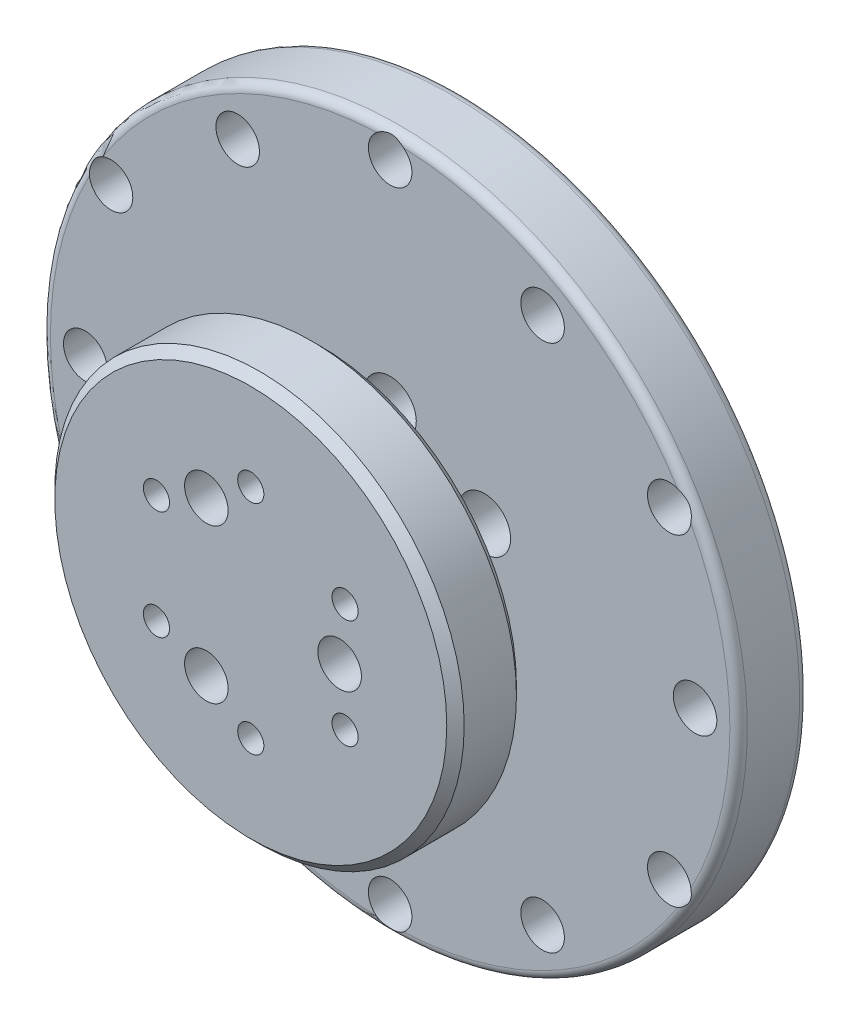
SolidWorks part; units mm, degrees
ref_plane "前视基准面" through (0, 0, 0) normal (0, 0, 1) x (1, 0, 0)
ref_plane "上视基准面" through (0, 0, 0) normal (0, 1, 0) x (1, 0, 0)
ref_plane "右视基准面" through (0, 0, 0) normal (1, 0, 0) x (0, 0, -1)
sketch "草图1" plane through (0, 0, 0) normal (0, 0, 1) x (1, 0, 0)
  circle A0 centre (0, 0) radius 23.5
extrude "凸台-拉伸3" add sketch "草图1" along normal blind 8
sketch "草图2" plane through (0, 0, 0) normal (0, 0, -1) x (-1, 0, 0)
  circle A1 centre (0, 12.5) radius 0.75
  circle A2 centre (10.8253, 6.25) radius 0.75
  circle A3 centre (10.8253, -6.25) radius 0.75
  circle A4 centre (0, -12.5) radius 0.75
  circle A5 centre (-10.8253, -6.25) radius 0.75
  circle A6 centre (-10.8253, 6.25) radius 0.75
extrude "切除-拉伸1" cut sketch "草图2" against normal blind 22
sketch "草图3" plane through (0, 0, 0) normal (0, 0, -1) x (-1, 0, 0)
  circle A0 centre (-10.8253, 6.25) radius 1.5
extrude "切除-拉伸2" cut sketch "草图3" against normal blind 22
sketch "草图4" plane through (0, 0, 0) normal (0, 0, -1) x (-1, 0, 0)
  circle A0 centre (0, 12.5) radius 1.5
extrude "切除-拉伸3" cut sketch "草图4" against normal blind 22
sketch "草图6" plane through (0, 0, 0) normal (0, 0, -1) x (-1, 0, 0)
  circle A0 centre (10.8253, 6.25) radius 1.5
extrude "切除-拉伸4" cut sketch "草图6" against normal blind 22
sketch "草图7" plane through (0, 0, 0) normal (0, 0, -1) x (-1, 0, 0)
  circle A0 centre (-10.8253, -6.25) radius 1.5
extrude "切除-拉伸5" cut sketch "草图7" against normal blind 22 contours A0
sketch "草图8" plane through (0, 0, 0) normal (0, 0, -1) x (-1, 0, 0)
  circle A0 centre (0, -12.5) radius 1.5
extrude "切除-拉伸6" cut sketch "草图8" against normal blind 22
sketch "草图9" plane through (0, 0, 0) normal (0, 0, -1) x (-1, 0, 0)
  circle A0 centre (10.8253, -6.25) radius 1.5
extrude "切除-拉伸7" cut sketch "草图9" against normal blind 22
sketch "草图12" plane through (0, 0, 0) normal (0, 0, -1) x (-1, 0, 0)
  circle A0 centre (-10.8253, 6.25) radius 2.75
extrude "切除-拉伸9" cut sketch "草图12" against normal blind 3.1
sketch "草图14" plane through (0, 0, 3.1) normal (0, 0, -1) x (-1, 0, 0)
  line L1 (-12.8649, 7.6785) -> (-12.3633, 7.6785)
  line L2 (-12.8649, 7.6785) -> (-12.8649, 6.9548)
  line L3 (-12.8649, 6.9548) -> (-12.3633, 6.9548)
  line L4 (-12.3633, 7.6785) -> (-12.3633, 6.9548)
extrude "凸台-拉伸4" add sketch "草图14" along normal up to surface (3.1 mm away) up to face at (8.0753, 6.25, 0)
sketch "草图15" plane through (0, 0, 0) normal (0, 0, -1) x (-1, 0, 0)
  circle A0 centre (-12.6234, 7.3733) radius 0.5468
extrude "切除-拉伸10" cut sketch "草图15" against normal blind 3.1
sketch "草图16" plane through (0, 0, 0) normal (0, 0, -1) x (-1, 0, 0)
  circle A0 centre (0, 12.5) radius 2.75
extrude "切除-拉伸11" cut sketch "草图16" against normal blind 3.1
sketch "草图17" plane through (0, 0, 0) normal (0, 0, -1) x (-1, 0, 0)
  circle A0 centre (10.8253, 6.25) radius 2.75
extrude "切除-拉伸12" cut sketch "草图17" against normal blind 3.1
sketch "草图18" plane through (0, 0, 0) normal (0, 0, -1) x (-1, 0, 0)
  circle A0 centre (10.8253, -6.25) radius 2.75
extrude "切除-拉伸13" cut sketch "草图18" against normal blind 3.1
sketch "草图19" plane through (0, 0, 0) normal (0, 0, -1) x (-1, 0, 0)
  circle A0 centre (0, -12.5) radius 2.75
extrude "切除-拉伸14" cut sketch "草图19" against normal blind 3.1
sketch "草图20" plane through (0, 0, 0) normal (0, 0, -1) x (-1, 0, 0)
  circle A0 centre (-10.8253, -6.25) radius 2.75
extrude "切除-拉伸15" cut sketch "草图20" against normal blind 3.1
sketch "草图21" plane through (0, 0, 8) normal (0, 0, 1) x (1, 0, 0)
  circle A0 centre (10.2, 0) radius 2.5
  circle A1 centre (-5.1, 8.8335) radius 2.5
  circle A2 centre (-5.1, -8.8335) radius 2.5
extrude "切除-拉伸17" cut sketch "草图21" against normal blind 5
sketch "草图22" plane through (0, 0, 0) normal (0, 0, -1) x (-1, 0, 0)
  circle A0 centre (0, 0) radius 9.75
extrude "凸台-拉伸5" add sketch "草图22" along normal blind 8
sketch "草图23" plane through (0, 0, -8) normal (0, 0, -1) x (-1, 0, 0)
  circle A0 centre (0, 0) radius 40
extrude "凸台-拉伸6" add sketch "草图23" along normal blind 8
sketch "草图25" plane through (0, 0, -16) normal (0, 0, -1) x (-1, 0, 0)
  circle A0 centre (0, 12.5) radius 3
  circle A1 centre (0, -12.5) radius 3
  circle A2 centre (10.8253, 6.25) radius 3
  circle A3 centre (10.8253, -6.25) radius 3
  circle A4 centre (-10.8253, 6.25) radius 3
  circle A5 centre (-10.8253, -6.25) radius 3
extrude "切除-拉伸18" cut sketch "草图25" against normal blind 10
sketch "草图26" plane through (0, 0, -16) normal (0, 0, -1) x (-1, 0, 0)
  circle A0 centre (0, 37) radius 2.5
  circle A1 centre (17.5, 30.3109) radius 2.5
  circle A2 centre (32.0429, 18.5) radius 2.5
  circle A3 centre (35, 0) radius 2.5
  circle A4 centre (32.0429, -18.5) radius 2.5
  circle A5 centre (17.5, -30.3109) radius 2.5
  circle A6 centre (0, -37) radius 2.5
  circle A7 centre (-17.5, -30.3109) radius 2.5
  circle A8 centre (-32.0429, -18.5) radius 2.5
  circle A9 centre (-35, 0) radius 2.5
  circle A10 centre (-32.0429, 18.5) radius 2.5
  circle A11 centre (-17.5, 30.3109) radius 2.5
extrude "切除-拉伸19" cut sketch "草图26" against normal blind 10
chamfer "倒角1" distance 1 angle 45 1 edges at (23.5, 0, 8)
chamfer "倒角2" distance 1 angle 45 1 edges at (23.5, 0, 0)
fillet "圆角1" radius 1 1 edges at (-40, 0, -8)
fillet "圆角2" radius 1 1 edges at (-40, 0, -16)
